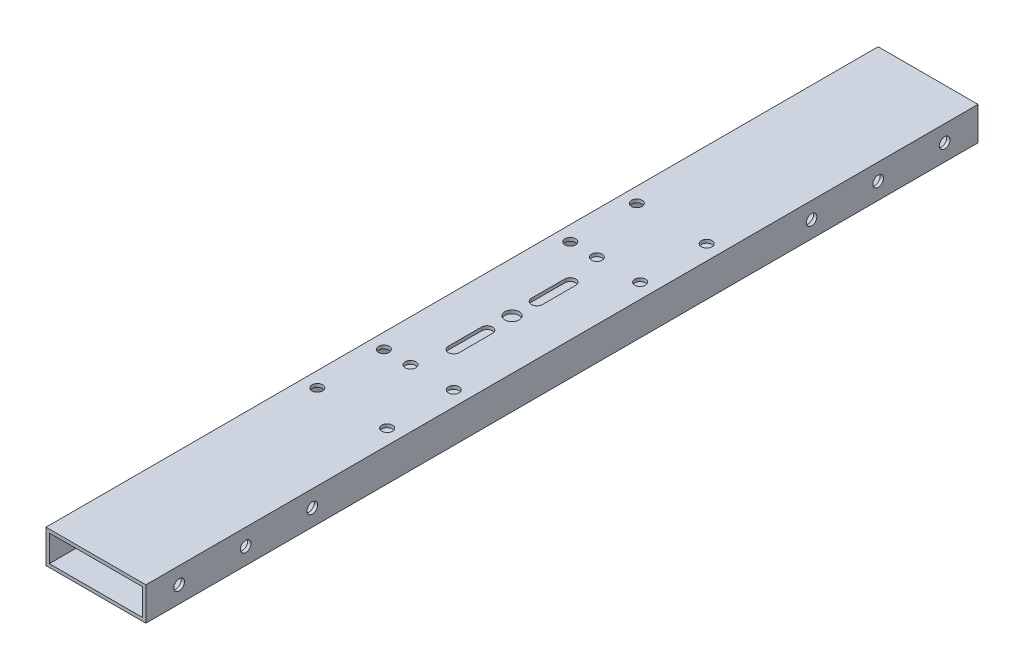
SolidWorks part; units mm, degrees
material "6061 合金"
ref_plane "前视基准面" through (0, 0, 0) normal (0, 0, 1) x (1, 0, 0)
ref_plane "上视基准面" through (0, 0, 0) normal (0, 1, 0) x (1, 0, 0)
ref_plane "右视基准面" through (0, 0, 0) normal (1, 0, 0) x (0, 0, -1)
other "Configuration Table"
sketch "草图1" plane through (0, 0, 0) normal (0, 0, 1) x (1, 0, 0)
  line L1 (-15, 5) -> (15, 5)
  line L2 (-15, 5) -> (-15, -5)
  line L3 (-15, -5) -> (15, -5)
  line L4 (15, 5) -> (15, -5)
  line L5 (-15, 5) -> (15, -5) construction
  line L6 (-15, -5) -> (15, 5) construction
  line L7 (-13.5, 3.5) -> (13.5, 3.5)
  line L8 (-13.5, 3.5) -> (-13.5, -3.5)
  line L9 (-13.5, -3.5) -> (13.5, -3.5)
  line L10 (13.5, 3.5) -> (13.5, -3.5)
  line L11 (-13.5, 3.5) -> (13.5, -3.5) construction
  line L12 (-13.5, -3.5) -> (13.5, 3.5) construction
  point P0 (0, 0)
  point P6 (0, 0)
  dimension "D1" = 1.5
  dimension "D2" = 1.5
  dimension "D3" = 10
  dimension "D4" = 30
extrude "凸台-拉伸1" add sketch "草图1" along normal blind 250
sketch "草图2" plane through (15, 0, 0) normal (1, 0, 0) x (0, 0, -1)
  line L0 (0, 0) -> (-281.3553, 0) construction
  line L1 (-250, -5) -> (-250, 5) construction
  line L2 (-240, 0) -> (-220, 0) construction
  line L3 (-125, 5) -> (-125, 97.1982) construction
  line L4 (-250, 5) -> (0, 5) construction
  circle A0 centre (-240, 0) radius 1.6
  circle A1 centre (-220, 0) radius 1.6
  circle A2 centre (-200, 0) radius 1.6
  circle A3 centre (-50, 0) radius 1.6
  circle A4 centre (-30, 0) radius 1.6
  circle A5 centre (-10, 0) radius 1.6
  dimension "D1" = 10
  dimension "D2" = 3.2
  dimension "D4" = 20
  dimension "D3" = 3
extrude "切除-拉伸1" cut sketch "草图2" against normal through all
sketch "草图3" plane through (0, 5, 0) normal (0, 1, 0) x (1, 0, 0)
  line L0 (4, 0) -> (4, -260.0948) construction
  line L1 (-15, -125) -> (203.3183, -125) construction
  line L2 (-15, -250) -> (-15, 0) construction
  line L3 (15, 0) -> (-15, 0) construction
  circle A0 centre (-2.5, -97) radius 1.6
  circle A1 centre (10.5, -97) radius 1.6
  circle A2 centre (-2.5, -153) radius 1.6
  circle A3 centre (10.5, -153) radius 1.6
  circle A4 centre (-2.5, -125) radius 1.6 construction
  circle A5 centre (10.5, -125) radius 1.6 construction
  circle A6 centre (10.5, -173) radius 1.6
  circle A7 centre (10.5, -77) radius 1.6
  circle A8 centre (-10.5, -173) radius 1.6
  circle A9 centre (-10.5, -153) radius 1.6
  circle A10 centre (-10.5, -77) radius 1.6
  circle A11 centre (-10.5, -97) radius 1.6
  dimension "D1" = 3.2
  dimension "D3" = 56
  dimension "D2" = 13
  dimension "D5" = 20
  dimension "D6" = 21
  dimension "D4" = 4
extrude "切除-拉伸2" cut sketch "草图3" against normal through all
sketch "草图4" plane through (0, 5, 0) normal (0, 1, 0) x (1, 0, 0)
  line L2 (-1.65, -107.5) -> (-1.65, -117.5)
  line L3 (1.65, -117.5) -> (1.65, -107.5)
  line L4 (-1.65, -107.5) -> (-1.65, -117.5)
  line L5 (1.65, -117.5) -> (1.65, -107.5)
  line L6 (1.65, -142.5) -> (1.65, -132.5)
  line L7 (-1.65, -132.5) -> (-1.65, -142.5)
  line L8 (1.65, -142.5) -> (1.65, -132.5)
  line L9 (-1.65, -132.5) -> (-1.65, -142.5)
  circle A1 centre (0, -125) radius 2.15
  circle A2 centre (0, -125) radius 2.15
  arc A4 (-1.65, -117.5) -> (1.65, -117.5) centre (0, -117.5) ccw
  arc A5 (1.65, -107.5) -> (-1.65, -107.5) centre (0, -107.5) ccw
  arc A6 (-1.65, -117.5) -> (1.65, -117.5) centre (0, -117.5) ccw
  arc A7 (1.65, -107.5) -> (-1.65, -107.5) centre (0, -107.5) ccw
  arc A8 (1.65, -132.5) -> (-1.65, -132.5) centre (0, -132.5) ccw
  arc A9 (-1.65, -142.5) -> (1.65, -142.5) centre (0, -142.5) ccw
  arc A10 (1.65, -132.5) -> (-1.65, -132.5) centre (0, -132.5) ccw
  arc A11 (-1.65, -142.5) -> (1.65, -142.5) centre (0, -142.5) ccw
  dimension "D1" = 0
  dimension "D2" = 0
  dimension "D3" = 0
extrude "切除-拉伸3" cut sketch "草图4" against normal through all
sketch "草图5" plane through (0, 5, 0) normal (0, 1, 0) x (1, 0, 0)
  line L0 (0, -15) -> (0, -65) construction
  line L1 (9, -15) -> (9, -65)
  line L2 (-9, -15) -> (-9, -65)
  line L3 (15, -250) -> (15, 0) construction
  line L4 (15, -125) -> (-58.6377, -125) construction
  line L5 (0, -235) -> (0, -185) construction
  line L6 (9, -235) -> (9, -185)
  line L7 (-9, -235) -> (-9, -185)
  arc A0 (9, -15) -> (-9, -15) centre (0, -15) ccw
  arc A1 (-9, -65) -> (9, -65) centre (0, -65) ccw
  arc A2 (9, -235) -> (-9, -235) centre (0, -235) cw
  arc A3 (-9, -185) -> (9, -185) centre (0, -185) cw
  point P2 (0, -40)
  point P14 (0, -210)
  dimension "D1" = 6
  dimension "D2" = 15
  dimension "D3" = 50
extrude "切除-拉伸4" [suppressed] cut sketch "草图5" against normal through all
sketch "草图6" plane through (0, 0, 0) normal (0, 0, -1) x (-1, 0, 0)
  line L0 (-13.5, 3.5) -> (13.5, 3.5) construction
  line L1 (-14, 4) -> (14, 4)
  line L2 (-14, 4) -> (-14, -4)
  line L3 (-14, -4) -> (14, -4)
  line L4 (14, 4) -> (14, -4)
  line L5 (13.5, 3.5) -> (13.5, -3.5) construction
  line L6 (13.5, -3.5) -> (-13.5, -3.5) construction
  line L7 (-13.5, -3.5) -> (-13.5, 3.5) construction
  dimension "D1" = 0.5
  dimension "D2" = 0.5
  dimension "D3" = 0.5
  dimension "D4" = 0.5
extrude "切除-拉伸5" cut sketch "草图6" against normal blind 330
